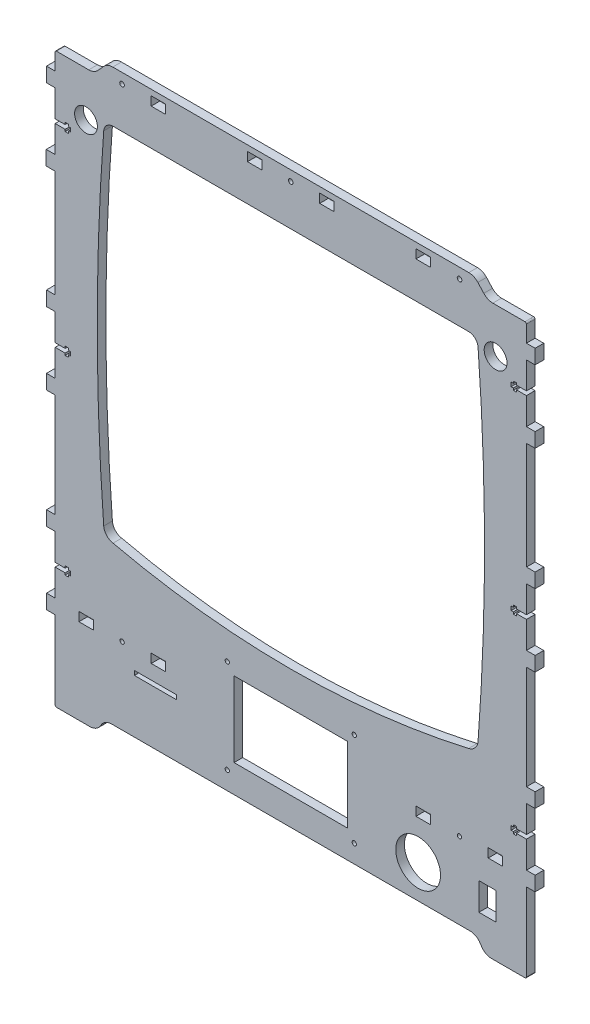
SolidWorks part; units mm, degrees
ref_plane "Спереди" through (0, 0, 0) normal (0, 0, 1) x (1, 0, 0)
ref_plane "Сверху" through (0, 0, 0) normal (0, 1, 0) x (1, 0, 0)
ref_plane "Справа" through (0, 0, 0) normal (1, 0, 0) x (0, 0, -1)
sketch "Эскиз1" plane through (0, 0, 0) normal (0, 0, 1) x (1, 0, 0)
  line L0 (-95.8892, 197.3491) -> (-85.8892, 197.3491)
  line L1 (-85.8892, 197.3491) -> (-85.8892, 191.1493)
  line L2 (-85.8892, 191.1493) -> (-95.8892, 191.1493)
  line L3 (-95.8892, 191.1493) -> (-95.8892, 197.3491)
  line L4 (97.3908, 191.1493) -> (87.3908, 191.1493)
  line L5 (87.3908, 191.1493) -> (87.3908, 197.3491)
  line L6 (87.3908, 197.3491) -> (97.3908, 197.3491)
  line L7 (97.3908, 197.3491) -> (97.3908, 191.1493)
  line L8 (97.3708, -142.9271) -> (87.3708, -142.9271)
  line L9 (87.3708, -142.9271) -> (87.3708, -136.7273)
  line L10 (87.3708, -136.7273) -> (97.3708, -136.7273)
  line L11 (97.3708, -136.7273) -> (97.3708, -142.9271)
  line L12 (147.3908, -142.9271) -> (137.3908, -142.9271)
  line L13 (137.3908, -142.9271) -> (137.3908, -136.7273)
  line L14 (137.3908, -136.7273) -> (147.3908, -136.7273)
  line L15 (147.3908, -136.7273) -> (147.3908, -142.9271)
  line L16 (-135.8892, -142.9271) -> (-145.8892, -142.9271)
  line L17 (-145.8892, -142.9271) -> (-145.8892, -136.7273)
  line L18 (-145.8892, -136.7273) -> (-135.8892, -136.7273)
  line L19 (-135.8892, -136.7273) -> (-135.8892, -142.9271)
  line L20 (-85.8692, -142.9271) -> (-95.8692, -142.9271)
  line L21 (-95.8692, -142.9271) -> (-95.8692, -136.7273)
  line L22 (-95.8692, -136.7273) -> (-85.8692, -136.7273)
  line L23 (-85.8692, -136.7273) -> (-85.8692, -142.9271)
  line L24 (-19.2392, 191.1493) -> (-29.2392, 191.1493)
  line L25 (-29.2392, 191.1493) -> (-29.2392, 197.3491)
  line L26 (-29.2392, 197.3491) -> (-19.2392, 197.3491)
  line L27 (-19.2392, 197.3491) -> (-19.2392, 191.1493)
  line L28 (30.7408, 191.1493) -> (20.7408, 191.1493)
  line L29 (20.7408, 191.1493) -> (20.7408, 197.3491)
  line L30 (20.7408, 197.3491) -> (30.7408, 197.3491)
  line L31 (30.7408, 197.3491) -> (30.7408, 191.1493)
  line L32 (-122.1926, 165.873) -> (123.8306, 165.873)
  line L33 (40.0508, -173.6757) -> (40.0508, -121.6757)
  line L34 (40.0508, -121.6757) -> (-38.5492, -121.6757)
  line L35 (-38.5492, -121.6757) -> (-38.5492, -173.6757)
  line L36 (-38.5492, -173.6757) -> (40.0508, -173.6757)
  line L37 (142.9388, -159.6762) -> (142.9388, -178.6762)
  line L38 (142.9388, -178.6762) -> (130.9388, -178.6762)
  line L39 (130.9388, -178.6762) -> (130.9388, -159.6762)
  line L40 (130.9388, -159.6762) -> (142.9388, -159.6762)
  line L41 (-162.3492, -146.9883) -> (-168.3492, -146.9883)
  line L42 (-168.3492, -146.9883) -> (-168.3492, -136.9883)
  line L43 (-168.3492, -136.9883) -> (-162.3492, -136.9883)
  line L44 (-162.3492, -136.9883) -> (-162.3492, -118.3783)
  line L45 (-162.3492, -96.9983) -> (-168.3492, -96.9983)
  line L46 (-168.3492, -96.9983) -> (-168.3492, -86.9983)
  line L47 (-168.3492, -86.9983) -> (-162.3492, -86.9983)
  line L48 (-162.3492, -86.9983) -> (-162.3492, -15.2683)
  line L49 (-162.3492, -15.2683) -> (-168.3492, -15.2683)
  line L50 (-162.3492, 34.7317) -> (-168.3492, 34.7317)
  line L51 (-168.3492, -5.2683) -> (-162.3492, -5.2683)
  line L52 (-168.3492, 44.7317) -> (-162.3492, 44.7317)
  line L53 (-162.3492, 118.8917) -> (-168.5253, 118.8917)
  line L54 (-168.5253, 118.8917) -> (-168.5253, 128.8917)
  line L55 (-168.5253, 128.8917) -> (-162.3492, 128.8917)
  line L56 (-162.3492, 128.8917) -> (-162.3492, 147.4917)
  line L57 (-162.3492, 168.8917) -> (-168.3492, 168.8917)
  line L58 (-168.3492, 168.8917) -> (-168.3492, 178.8917)
  line L59 (-168.3492, 178.8917) -> (-162.3492, 178.8917)
  line L60 (-162.3492, 178.8917) -> (-162.3492, 190.2917)
  line L61 (-162.3492, -201.0283) -> (-162.3492, -146.9883)
  line L62 (163.8508, -146.9883) -> (169.8508, -146.9883)
  line L63 (169.8508, -146.9883) -> (169.8508, -136.9883)
  line L64 (169.8508, -136.9883) -> (163.8509, -136.9883)
  line L65 (163.8509, -136.9883) -> (163.8509, -118.3783)
  line L66 (163.9388, -96.9983) -> (169.8508, -96.9983)
  line L67 (169.8508, -96.9983) -> (169.8508, -86.9983)
  line L68 (169.8508, -86.9983) -> (163.8508, -86.9983)
  line L69 (163.8508, -86.9983) -> (163.8508, -15.2683)
  line L70 (163.8508, -15.2683) -> (169.8508, -15.2683)
  line L71 (163.8508, 34.7317) -> (169.8508, 34.7317)
  line L72 (169.8508, -5.2683) -> (163.8508, -5.2683)
  line L73 (169.8508, 44.7317) -> (163.8508, 44.7317)
  line L74 (163.8508, 118.8917) -> (169.8508, 118.8917)
  line L75 (169.8508, 118.8917) -> (169.8508, 128.8917)
  line L76 (169.8508, 128.8917) -> (163.8508, 128.8917)
  line L77 (163.8508, 128.8917) -> (163.8508, 147.4917)
  line L78 (163.8508, 168.8917) -> (169.8508, 168.8917)
  line L79 (169.8508, 168.8917) -> (169.8508, 178.8917)
  line L80 (169.8508, 178.8917) -> (163.8508, 178.8917)
  line L81 (163.8508, 178.8917) -> (163.8508, 190.2917)
  line L82 (156.9388, 150.2917) -> (156.9388, 151.6918)
  line L83 (163.9388, -115.5783) -> (156.9388, -115.5783)
  line L84 (156.9388, -114.1782) -> (154.7379, -114.1782)
  line L85 (156.9414, -118.3771) -> (163.8509, -118.3783)
  line L86 (153.2404, -118.378) -> (154.7404, -118.3772)
  line L87 (-155.4373, 11.9316) -> (-153.2365, 11.9316)
  line L88 (154.7379, -114.1782) -> (154.7388, -115.5781)
  line L89 (154.7388, 16.1319) -> (153.2388, 16.131)
  line L90 (153.2388, -115.579) -> (153.2404, -118.378)
  line L91 (-155.4373, -119.7784) -> (-153.2365, -119.7784)
  line L92 (163.8508, 150.2917) -> (156.9388, 150.2917)
  line L93 (156.9413, -119.7781) -> (156.9414, -118.3771)
  line L94 (156.9388, -115.5783) -> (156.9388, -114.1782)
  line L95 (154.7388, -115.5781) -> (153.2388, -115.579)
  line L96 (154.7404, 147.4928) -> (154.7412, 146.0919)
  line L97 (-155.4398, -114.1795) -> (-155.4398, -115.5795)
  line L98 (154.7404, 13.3328) -> (154.7412, 11.9319)
  line L99 (-162.3492, 147.4917) -> (-155.4373, 147.4917)
  line L100 (-155.4373, 147.4917) -> (-155.4373, 146.0916)
  line L101 (-155.4398, 150.2905) -> (-162.3492, 150.2917)
  line L102 (-153.2389, 150.2895) -> (-153.2398, 151.6905)
  line L103 (154.7404, -118.3772) -> (154.7412, -119.7781)
  line L104 (-155.4398, -115.5795) -> (-162.3492, -115.5783)
  line L105 (154.7379, 151.6918) -> (154.7388, 150.2919)
  line L106 (156.9412, 146.0919) -> (156.9413, 147.4929)
  line L107 (-153.2373, 13.3033) -> (-151.7373, 13.3041)
  line L108 (-155.4373, -118.3783) -> (-155.4373, -119.7784)
  line L109 (153.2388, 150.291) -> (153.2404, 147.492)
  line L110 (-153.2398, 17.5305) -> (-155.4398, 17.5305)
  line L111 (-162.3492, 13.3317) -> (-155.4373, 13.3317)
  line L112 (154.7412, 146.0919) -> (156.9412, 146.0919)
  line L113 (153.2404, 147.492) -> (154.7404, 147.4928)
  line L114 (-153.2373, 147.4915) -> (-151.7373, 147.4924)
  line L115 (-151.7373, 13.3041) -> (-151.7389, 16.1304)
  line L116 (163.8508, 16.1317) -> (156.9388, 16.1317)
  line L117 (154.7379, 17.5047) -> (154.7388, 16.1319)
  line L118 (154.7388, 150.2919) -> (153.2388, 150.291)
  line L119 (154.7412, 11.9319) -> (156.9412, 11.9319)
  line L120 (-153.2398, -114.1795) -> (-155.4398, -114.1795)
  line L121 (-151.7373, -118.3776) -> (-151.7389, -115.5796)
  line L122 (-153.2373, -118.3785) -> (-151.7373, -118.3776)
  line L123 (-153.2365, 11.9316) -> (-153.2373, 13.3033)
  line L124 (156.9413, 13.3329) -> (163.8508, 13.3317)
  line L125 (-162.3492, -118.3783) -> (-155.4373, -118.3783)
  line L126 (153.2388, 16.131) -> (153.2404, 13.332)
  line L127 (-153.2389, -115.5805) -> (-153.2398, -114.1795)
  line L128 (-151.7389, 16.1304) -> (-153.2389, 16.1295)
  line L129 (-155.4373, 146.0916) -> (-153.2365, 146.0916)
  line L130 (-153.2365, -119.7784) -> (-153.2373, -118.3785)
  line L131 (-155.4398, 151.6905) -> (-155.4398, 150.2905)
  line L132 (-151.7389, -115.5796) -> (-153.2389, -115.5805)
  line L133 (-153.2365, 146.0916) -> (-153.2373, 147.4915)
  line L134 (153.2404, 13.332) -> (154.7404, 13.3328)
  line L135 (156.9388, 151.6918) -> (154.7379, 151.6918)
  line L136 (-151.7373, 147.4924) -> (-151.7389, 150.2904)
  line L137 (156.9413, 147.4929) -> (163.8508, 147.4917)
  line L138 (-155.4398, 16.1305) -> (-162.3492, 16.1317)
  line L139 (156.9412, 11.9319) -> (156.9413, 13.3329)
  line L140 (-155.4398, 17.5305) -> (-155.4398, 16.1305)
  line L141 (154.7412, -119.7781) -> (156.9413, -119.7781)
  line L142 (-153.2398, 151.6905) -> (-155.4398, 151.6905)
  line L143 (156.9388, 17.5047) -> (154.7379, 17.5047)
  line L144 (-151.7389, 150.2904) -> (-153.2389, 150.2895)
  line L145 (-162.3492, -115.5783) -> (-162.3492, -96.9983)
  line L146 (-162.3492, 150.2917) -> (-162.3492, 168.8917)
  line L147 (163.9388, -115.5783) -> (163.9388, -96.9983)
  line L148 (163.8508, 150.2917) -> (163.8508, 168.8917)
  line L149 (-139.0924, 191.2917) -> (-161.5253, 191.2917)
  line L150 (-128.7242, 198.5304) -> (-132.8221, 194.053)
  line L151 (123.9554, 201.2917) -> (-122.4539, 201.2917)
  line L152 (130.2257, 198.5304) -> (134.3236, 194.053)
  line L153 (140.5939, 191.2917) -> (162.8508, 191.2917)
  line L154 (-131.8015, -198.972) -> (-129.7448, -195.9523)
  line L155 (162.7628, -202.0051) -> (139.7264, -202.0051)
  line L156 (133.303, -198.972) -> (131.2463, -195.9523)
  line L157 (-161.4373, -202.0083) -> (-138.3129, -202.0083)
  line L158 (-123.2334, -192.916) -> (124.7349, -192.916)
  line L159 (163.8508, -201.0305) -> (163.8508, -146.9883)
  line L160 (-162.3492, 13.3317) -> (-162.3492, -5.2683)
  line L161 (-168.3492, -15.2683) -> (-168.3492, -5.2683)
  line L162 (-168.3492, 34.7317) -> (-168.3492, 44.7317)
  line L163 (-162.3492, 44.7317) -> (-162.3492, 118.8917)
  line L164 (163.8508, 13.3317) -> (163.8508, -5.2683)
  line L165 (169.8508, -15.2683) -> (169.8508, -5.2683)
  line L166 (169.8508, 34.7317) -> (169.8508, 44.7317)
  line L167 (163.8508, 44.7317) -> (163.8508, 118.8917)
  line L168 (-155.4373, 13.3317) -> (-155.4373, 11.9316)
  line L169 (-153.2389, 16.1295) -> (-153.2398, 17.5305)
  line L170 (156.9388, 16.1317) -> (156.9388, 17.5047)
  line L171 (-162.3492, 34.7317) -> (-162.3492, 16.1317)
  line L172 (163.8508, 34.7317) -> (163.8508, 16.1317)
  line L173 (-107.5042, -155.9271) -> (-107.5042, -152.9271)
  line L174 (-107.5042, -152.9271) -> (-78.5042, -152.9271)
  line L175 (-78.5042, -152.9271) -> (-78.5042, -155.9271)
  line L176 (-78.5042, -155.9271) -> (-107.5042, -155.9271)
  arc A0 (-122.2646, -84.0153) -> (123.8554, -84.0153) centre (0.7954, 449.8336) ccw
  arc A1 (-128.7276, 159.8968) -> (-128.7407, -76.9742) centre (1428.8347, 41.3753) ccw
  arc A2 (130.3319, -76.9742) -> (130.3653, 159.8968) centre (-1430.2964, 41.6814) ccw
  circle A3 centre (44.7108, -115.4257) radius 1.5
  circle A4 centre (44.7108, -180.4257) radius 1.5
  circle A5 centre (-43.2092, -180.4257) radius 1.5
  circle A6 centre (-43.2092, -115.4257) radius 1.5
  circle A7 centre (88.8942, -169.8279) radius 15.5
  arc A8 (130.3653, 159.8968) -> (123.8306, 165.873) centre (123.8306, 159.3123) ccw
  arc A9 (-122.1926, 165.873) -> (-128.7276, 159.8968) centre (-122.2654, 159.3916) ccw
  arc A10 (-128.7407, -76.9742) -> (-122.2646, -84.0153) centre (-121.0385, -76.3888) ccw
  arc A11 (123.8554, -84.0153) -> (130.3319, -76.9742) centre (121.9542, -75.7674) ccw
  circle A12 centre (0.7508, 194.2417) radius 1.6
  circle A13 centre (-116.0492, 194.2417) radius 1.6
  arc A14 (134.3236, 194.053) -> (140.5939, 191.2917) centre (140.5939, 199.7917) ccw
  arc A15 (-161.5253, 191.2917) -> (-162.3492, 190.2917) centre (-161.4373, 190.3797) ccw
  arc A16 (-139.0924, 191.2917) -> (-132.8221, 194.053) centre (-139.0924, 199.7917) ccw
  arc A17 (-122.4539, 201.2917) -> (-128.7242, 198.5304) centre (-122.4539, 192.7917) ccw
  circle A18 centre (117.5508, 194.2417) radius 1.6
  arc A19 (130.2257, 198.5304) -> (123.9554, 201.2917) centre (123.9554, 192.7917) ccw
  arc A20 (163.8508, 190.2917) -> (162.8508, 191.2917) centre (162.8508, 190.2917) ccw
  arc A21 (-123.2334, -192.916) -> (-129.7448, -195.9523) centre (-123.2334, -201.416) ccw
  arc A22 (-138.3129, -202.0083) -> (-131.8015, -198.972) centre (-138.3129, -193.5083) ccw
  arc A23 (131.2463, -195.9523) -> (124.7349, -192.916) centre (124.7349, -201.416) ccw
  arc A24 (133.303, -198.972) -> (139.7264, -202.0051) centre (139.7677, -193.5994) ccw
  arc A25 (-162.3492, -201.0283) -> (-161.4373, -202.0083) centre (-161.3926, -201.0524) ccw
  arc A26 (162.7628, -202.0051) -> (163.8508, -201.0305) centre (162.8081, -200.9612) ccw
  circle A27 centre (-140.9992, 160.2917) radius 7.9
  circle A28 centre (142.5008, 160.2917) radius 7.9
  circle A29 centre (-115.9892, -139.8588) radius 1.5
  circle A30 centre (117.4908, -139.8477) radius 1.5
  point P239 (87.3908, 194.2492)
  dimension "D11" = 15.8
  dimension "D12" = 15.8
  dimension "D53" = 31
  dimension "D1" = 10
  dimension "D2" = 12.4
  dimension "D3" = 12.4
  dimension "D4" = 10
  dimension "D5" = 18.6
  dimension "D6" = 2.8
  dimension "D7" = 18.6
  dimension "D8" = 10
  dimension "D9" = 10
  dimension "D10" = 10
  dimension "D13" = 6.1761
  dimension "D15" = 18.6
  dimension "D16" = 10
  dimension "D17" = 74.16
  dimension "D18" = 74.16
  dimension "D19" = 10
  dimension "D20" = 10
  dimension "D21" = 18.6
  dimension "D22" = 18.6
  dimension "D23" = 18.6
  dimension "D24" = 18.6
  dimension "D25" = 10
  dimension "D26" = 10
  dimension "D27" = 71.73
  dimension "D28" = 71.73
  dimension "D29" = 10
  dimension "D30" = 10
  dimension "D31" = 18.58
  dimension "D32" = 18.58
  dimension "D33" = 18.61
  dimension "D34" = 18.61
  dimension "D35" = 10
  dimension "D36" = 10
  dimension "D37" = 54.04
  dimension "D38" = 54.0422
  dimension "D39" = 403.2968
  dimension "D40" = 2.8
  dimension "D41" = 2.8
  dimension "D42" = 2.8
  dimension "D43" = 2.8
  dimension "D44" = 403.3
  dimension "D45" = 10
  dimension "D46" = 10
  dimension "D47" = 10
  dimension "D48" = 10
  dimension "D49" = 10
  dimension "D50" = 10
  dimension "D51" = 10
  dimension "D52" = 10
  dimension "D54" = 338.2
  dimension "D55" = 169.1
  dimension "D56" = 169.1
  dimension "D57" = 52.3
  dimension "D58" = 52.3
  dimension "D59" = 72.46
  dimension "D60" = 72.46
  dimension "D61" = 56.65
  dimension "D62" = 56.65
  dimension "D63" = 19.99
  dimension "D64" = 19.99
  dimension "D65" = 21.35
  dimension "D66" = 21.35
  dimension "D67" = 22.46
  dimension "D68" = 22.46
  dimension "D69" = 19.9
  dimension "D70" = 19.9
  dimension "D71" = 20.12
  dimension "D72" = 20.12
  dimension "D73" = 47.32
  dimension "D74" = 78.6
  dimension "D75" = 47.32
  dimension "D76" = 4.66
  dimension "D77" = 4.66
  dimension "D78" = 4.66
  dimension "D79" = 4.66
  dimension "D80" = 6.25
  dimension "D81" = 6.25
  dimension "D82" = 6.75
  dimension "D83" = 6.75
  dimension "D84" = 55.02
  dimension "D85" = 6
extrude "Бобышка-Вытянуть2" add sketch "Эскиз1" along normal blind 6 contours A5 | A4 | A3 | A13 | A12 | A7 | A6 | L32 A8 A2 A11 A0 A10 A1 A9 | A18 | A30 | A29 | A28 | A27 | L4 L5 L6 L7 | L0 L1 L2 L3 | L20 L21 L22 L23 | L16 L17 L18 L19 | L12 L13 L14 L15 | L8 L9 L10 L11 | L37 L38 L39 L40 | L33 L34 L35 L36 | L28 L29 L30 L31 | L24 L25 L26 L27 | L41 L42 L43 L44 L125 L108 L91 L130 L122 L121 L132 L127 L120 L97 L104 L145 L45 L46 L47 L48 L49 L161 L51 L160 L111 L168 L87 L123 L107 L115 L128 L169 L110 L140 L138 L171 L50 L162 L52 L163 L53 L54 L55 L56 L99 L100 L129 L133 L114 L136 L144 L102 L142 L131 L101 L146 L57 L58 L59 L60 A15 L149 A16 L150 A17 L151 A19 L152 A14 L153 A20 L81 L80 L79 L78 L148 L92 L82 L135 L105 L118 L109 L113 L96 L112 L106 L137 L77 L76 L75 L74 L167 L73 L166 L71 L172 L116 L170 L143 L117 L89 L126 L134 L98 L119 L139 L124 L164 L72 L165 L70 L69 L68 L67 L66 L147 L83 L94 L84 L88 L95 L90 L86 L103 L141 L93 L85 L65 L64 L63 L62 L159 A26 L155 A24 L156 A23 L158 A21 L154 A22 L157 A25 L61 | L173 L174 L175 L176
